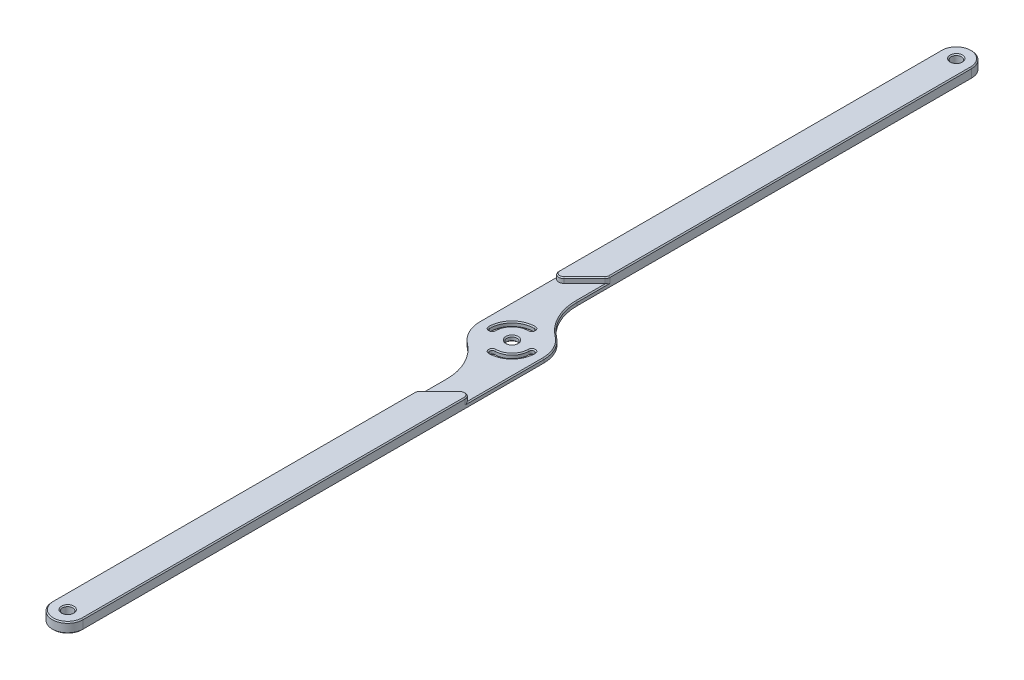
SolidWorks part; units mm, degrees
ref_plane "前视基准面" through (0, 0, 0) normal (0, 0, 1) x (1, 0, 0)
ref_plane "上视基准面" through (0, 0, 0) normal (0, 1, 0) x (1, 0, 0)
ref_plane "右视基准面" through (0, 0, 0) normal (1, 0, 0) x (0, 0, -1)
other "Configuration Table"
sketch "草图1" plane through (0, 0, 0) normal (0, 1, 0) x (1, 0, 0)
  line L0 (-36.5646, -28.9901) -> (-32.5646, -24.9901)
  line L1 (-37.2867, 79.5751) -> (-37.2867, 8.9893)
  line L2 (-43.2867, 79.5751) -> (-43.2867, 4.9893)
  line L4 (-30.8574, -25.6972) -> (-30.8574, -100.283)
  line L5 (-36.8574, -4.1393) -> (-36.8574, -4.143)
  line L6 (-41.5796, 4.2822) -> (-37.5796, 8.2822)
  line L8 (-37.2867, -16.5686) -> (-36.8574, -16.5686)
  line L9 (-37.0721, -4.1393) -> (-37.2867, -4.1393)
  line L10 (-37.0721, -4.1393) -> (-36.8574, -4.1393)
  line L12 (-43.2867, -10.354) -> (-43.2867, 4.9893)
  line L18 (-37.2867, 8.9893) -> (-37.2867, 2.5751)
  line L21 (-36.8574, -23.283) -> (-36.8574, -29.6972)
  line L22 (-36.8574, -29.6972) -> (-36.8574, -100.283)
  line L23 (-37.2867, -16.5649) -> (-37.2867, -16.5686)
  line L24 (-30.8574, -10.354) -> (-30.8574, -25.6972)
  arc A4 (-30.8574, -10.354) -> (-33.3216, -5.3986) centre (-37.0721, -10.354) ccw
  arc A10 (-43.2867, -10.354) -> (-40.8225, -15.3093) centre (-37.0721, -10.354) ccw
  arc A11 (-33.3216, -5.3986) -> (-37.2867, 2.5751) centre (-27.2867, 2.5751) cw
  arc A12 (-36.8574, -23.283) -> (-40.8225, -15.3093) centre (-46.8574, -23.283) ccw
  arc A15 (-37.2867, 8.9893) -> (-37.5796, 8.2822) centre (-38.2867, 8.9893) cw
  arc A16 (-43.2867, 4.9893) -> (-41.5796, 4.2822) centre (-42.2867, 4.9893) ccw
  arc A17 (-36.8574, -29.6972) -> (-36.5646, -28.9901) centre (-35.8574, -29.6972) cw
  arc A18 (-30.8574, -25.6972) -> (-32.5646, -24.9901) centre (-31.8574, -25.6972) ccw
  arc A22 (-36.8574, -100.283) -> (-30.8574, -100.283) centre (-33.8574, -100.283) ccw
  arc A23 (-37.2867, 79.5751) -> (-43.2867, 79.5751) centre (-40.2867, 79.5751) ccw
  circle A24 centre (-40.2867, 79.5751) radius 1
  circle A25 centre (-33.8574, -100.283) radius 1
  point P2 (-40.2867, -10.354)
  point P9 (-33.8574, -10.354)
extrude "凸台-拉伸1" add sketch "草图1" along normal blind 2 contours L1 L2 L6 | L22 L4 L0 region at (-33.8246, 0, 64.3072) region at (-40.3196, 0, -43.5992)
extrude "凸台-拉伸2" add sketch "草图1<3>" along normal blind 1 contours A12 L22 L0 L4 A4 A11 L1 L6 L2 A10 region at (-37.0721, 0, 10.354)
sketch "草图1<3>" plane through (0, 0, 0) normal (0, 1, 0) x (1, 0, 0) same geometry as "草图1"
sketch "草图2" plane through (0, 1, 0) normal (0, 1, 0) x (1, 0, 0)
  arc A1 (-40.9267, -10.354) -> (-37.0721, -6.4994) centre (-37.0721, -10.354) cw construction
  arc A2 (-37.0721, -5.9994) -> (-41.4267, -10.354) centre (-37.0721, -10.354) ccw
  arc A3 (-37.0721, -6.9994) -> (-40.4267, -10.354) centre (-37.0721, -10.354) ccw
  arc A4 (-37.0721, -6.9994) -> (-37.0721, -5.9994) centre (-37.0721, -6.4994) ccw
  arc A5 (-41.4267, -10.354) -> (-40.4267, -10.354) centre (-40.9267, -10.354) ccw
  arc A6 (-37.0721, -14.2085) -> (-33.2175, -10.354) centre (-37.0721, -10.354) ccw construction
  arc A7 (-37.0721, -14.7085) -> (-32.7175, -10.354) centre (-37.0721, -10.354) ccw
  arc A8 (-37.0721, -13.7085) -> (-33.7175, -10.354) centre (-37.0721, -10.354) ccw
  arc A9 (-37.0721, -13.7085) -> (-37.0721, -14.7085) centre (-37.0721, -14.2085) ccw
  arc A10 (-32.7175, -10.354) -> (-33.7175, -10.354) centre (-33.2175, -10.354) ccw
  circle A11 centre (-37.0721, -10.354) radius 1
  point P4 (-39.7977, -7.6284)
  point P15 (-34.3465, -13.0796)
extrude "切除-拉伸1" cut sketch "草图2" against normal blind 3.5
chamfer "倒角1" distance 0.2 angle 45 16 edges at (-30.8574, 0, 55.3185) (-31.5075, 0, 7.5868) (-36.2407, 0, 1.8775) (-36.8574, 0, 61.783) (-37.2867, 0, -41.0751) (-37.9034, 0, 18.8304) (-42.6367, 0, 13.1211) (-43.2867, 0, -34.6106) (-37.3628, 2, -8.6066) (-37.2867, 2, -44.2822) (-39.5796, 2, -6.2822) (-42.6694, 2, -4.0654) (-43.2867, 2, -42.2822) (-33.8574, 0, 103.283) (-40.2867, 0, -82.5751) (-40.2867, 2, -82.5751)
chamfer "倒角2" distance 0.2 angle 45 6 edges at (-36.7813, 2, 29.3146) (-34.5646, 2, 26.9901) (-36.8574, 2, 64.9901) (-31.4748, 2, 24.7734) (-30.8574, 2, 62.9901) (-33.8574, 2, 103.283)
chamfer "倒角4" distance 0.2 angle 45 4 edges at (-37.2867, 1, -5.7822) (-36.2407, 1, 1.8775) (-31.5075, 1, 7.5868) (-30.8574, 1, 18.0256)
chamfer "倒角5" distance 0.2 angle 45 20 edges at (-33.9929, 0, 13.4331) (-33.2175, 0, 9.854) (-37.5721, 0, 14.2085) (-34.7, 0, 12.726) (-33.9929, 1, 13.4331) (-33.2175, 1, 9.854) (-37.5721, 1, 14.2085) (-34.7, 1, 12.726) (-37.0721, 0, 11.354) (-37.0721, 1, 11.354) (-39.4441, 1, 7.9819) (-36.5721, 1, 6.4994) (-40.9267, 1, 10.854) (-40.1512, 1, 7.2748) (-39.4441, 0, 7.9819) (-36.5721, 0, 6.4994) (-40.9267, 0, 10.854) (-40.1512, 0, 7.2748) (-40.2867, 2, -78.5751) (-40.2867, 0, -78.5751)
chamfer "倒角6" distance 0.2 angle 45 2 edges at (-33.8574, 0, 101.283) (-33.8574, 2, 101.283)
